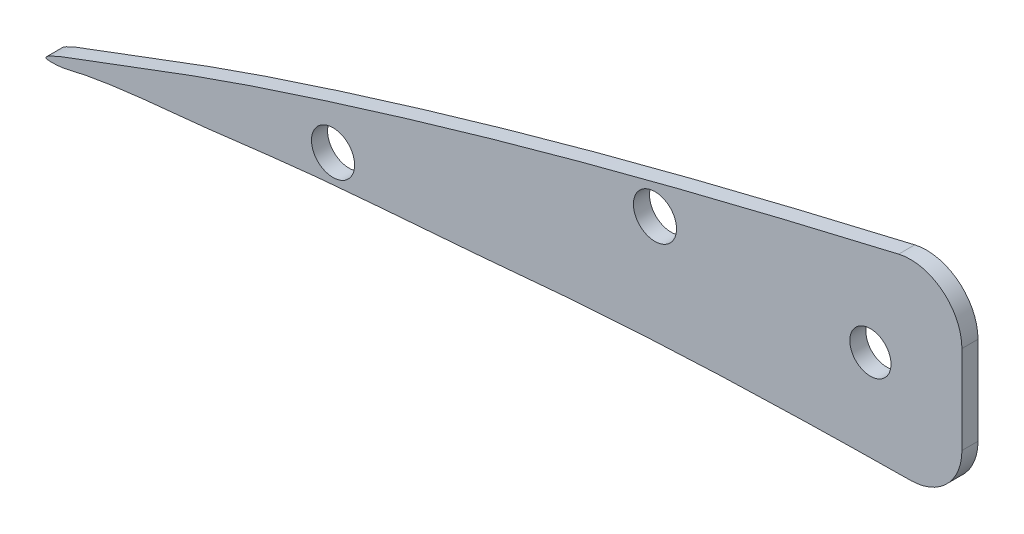
SolidWorks part; units mm, degrees
material "Balsa"
ref_plane "Front Plane" through (0, 0, 0) normal (0, 0, 1) x (1, 0, 0)
ref_plane "Top Plane" through (0, 0, 0) normal (0, 1, 0) x (1, 0, 0)
ref_plane "Right Plane" through (0, 0, 0) normal (1, 0, 0) x (0, 0, -1)
sketch "Sketch1" plane through (0, 0, 0) normal (0, 0, 1) x (1, 0, 0)
  line L0 (99.3264, 18.4044) -> (99.3264, -2.9864)
  line L1 (73.9264, 12.4163) -> (99.3264, -2.9864) construction
  line L8 (238.3754, -9.6537) -> (238.3754, -27.8289) construction
  line L9 (73.9264, -3.3744) -> (73.9264, 12.4163) construction
  line L10 (238.3754, -9.6537) -> (3.4483, -9.6537) construction
  line L11 (73.9264, -3.3744) -> (73.9264, 12.4163) construction
  line L12 (99.3264, 18.4044) -> (73.9264, -3.3744) construction
  spline S0 degree 3 poles (5.0476, -9.6537) (1.3045, -10.0425) (11.5033, -6.3535) (19.7236, -3.0928) (52.9152, 7.6459) (77.8898, 13.46) (99.3264, 18.4044) knots 0 0 0 0 0.059915 0.175786 0.369275 1 1 1 1
  spline S1 degree 3 poles (5.0476, -9.6537) (9.4826, -8.5461) (16.9885, -8.0769) (30.3366, -6.2544) (41.9467, -5.566) (65.8658, -3.2313) (83.9748, -3.0891) (99.3264, -2.9864) knots 0 0 0 0 0.144322 0.237948 0.427123 0.512832 1 1 1 1
  spline S6 degree 3 poles (5.0476, -9.6537) (9.4826, -8.5461) (16.9885, -8.0769) (30.3366, -6.2543) (41.9468, -5.5667) (60.7635, -3.7271) (83.9252, -2.9983) (119.6066, -2.8533) (155.1663, -4.9989) (188.2936, -10.0956) (210.9238, -14.2463) (226.8417, -14.3145) (237.449, -14.868) (238.3754, -9.6537) knots 0 0 0 0 0.057787 0.095275 0.171021 0.205339 0.335319 0.464904 0.658702 0.785512 0.893517 0.943092 1 1 1 1 construction
  spline S7 degree 3 poles (238.3754, -9.6537) (237.7653, -4.112) (231.8626, 3.793) (218.5807, 12.9188) (199.1338, 22.0262) (170.9048, 27.4643) (139.4251, 26.4056) (107.9057, 20.4989) (74.2413, 12.6461) (44.8793, 5.0523) (19.7218, -3.094) (11.5035, -6.3533) (1.3045, -10.0425) (5.0476, -9.6537) knots 0 0 0 0 0.060864 0.113688 0.188609 0.312909 0.448482 0.557612 0.691544 0.852438 0.929756 0.976058 1 1 1 1 construction
  dimension "D1" = 25.4
  dimension "D3" = 164.449
  dimension "D4" = 234.9271
extrude "Boss-Extrude1" add sketch "Sketch1" along normal blind 226.06
sketch "Sketch2" plane through (0, 0, 0) normal (0, 1, 0) x (1, 0, 0)
  line L0 (169.6815, 0) -> (169.6815, -226.06)
  line L1 (169.6815, -226.06) -> (73.1644, -226.06)
  line L2 (73.1644, -226.06) -> (73.1644, -197.485)
  line L3 (73.1644, -197.485) -> (93.7384, -197.485)
  line L4 (93.7384, -197.485) -> (93.7384, -28.575)
  line L5 (93.7384, -28.575) -> (73.1644, -28.575)
  line L6 (73.1644, -28.575) -> (73.1644, 0)
  line L7 (73.1644, 0) -> (169.6815, 0)
  line L8 (3.4109, -226.06) -> (99.3264, -226.06) construction
  line L9 (99.3264, 0) -> (3.4109, 0) construction
  line L10 (99.3264, -226.06) -> (99.3264, 0) construction
  dimension "D1" = 20.574
  dimension "D2" = 5.588
  dimension "D3" = 75.9431
  dimension "D4" = 28.575
  dimension "D5" = 0
  dimension "D6" = 0
extrude "Cut-Extrude1" cut sketch "Sketch2" against normal through all both and the other way through all
fillet "Fillet1" radius 5.08 6 edges at (73.1644, -3.3889, 14.2875) (73.1644, 12.236, 14.2875) (93.7384, -3.0267, 113.03) (93.7384, 17.1136, 113.03) (73.1644, -3.3889, 211.7725) (73.1644, 12.236, 211.7725)
sketch "Sketch4" plane through (0, 0, 0) normal (1, 0, 0) x (0, 0, -1)
  line L0 (-197.485, 2.0054) -> (-197.485, 10.7162) construction
  line L1 (-238.6023, -25.5438) -> (-197.485, -25.5438)
  line L2 (-238.6023, -25.5438) -> (-238.6023, 42.1009)
  line L3 (-238.6023, 42.1009) -> (-197.485, 42.1009)
  line L4 (-197.485, -25.5438) -> (-197.485, 42.1009)
  line L6 (-195.8975, 42.1009) -> (15.385, 42.1009)
  line L7 (-195.8975, 42.1009) -> (-195.8975, -39.6297)
  line L8 (-195.8975, -39.6297) -> (15.385, -39.6297)
  line L9 (15.385, 42.1009) -> (15.385, -39.6297)
  dimension "D1" = 1.5875
extrude "Cut-Extrude5" cut sketch "Sketch4" along normal through all
sketch "Sketch3" plane through (0, 0, 0) normal (0, 0, 1) x (1, 0, 0)
  line L8 (238.3754, -9.6537) -> (238.3754, -27.8289) construction
  circle A0 centre (84.7136, 5.8749) radius 2.032
  dimension "D1" = 4.064
extrude "Cut-Extrude2" cut sketch "Sketch3" along normal through all
sketch "Sketch5" plane through (0, 0, 197.485) normal (0, 0, 1) x (1, 0, 0)
  circle A2 centre (31.7176, -3.5577) radius 2.127
  circle A3 centre (63.4676, 6.8563) radius 2.127
  dimension "D1" = 4.254
  dimension "D2" = 26.67
  dimension "D3" = 58.42
  dimension "D4" = 6.096
  dimension "D5" = 16.51
extrude "Cut-Extrude6" cut sketch "Sketch5" against normal through all
